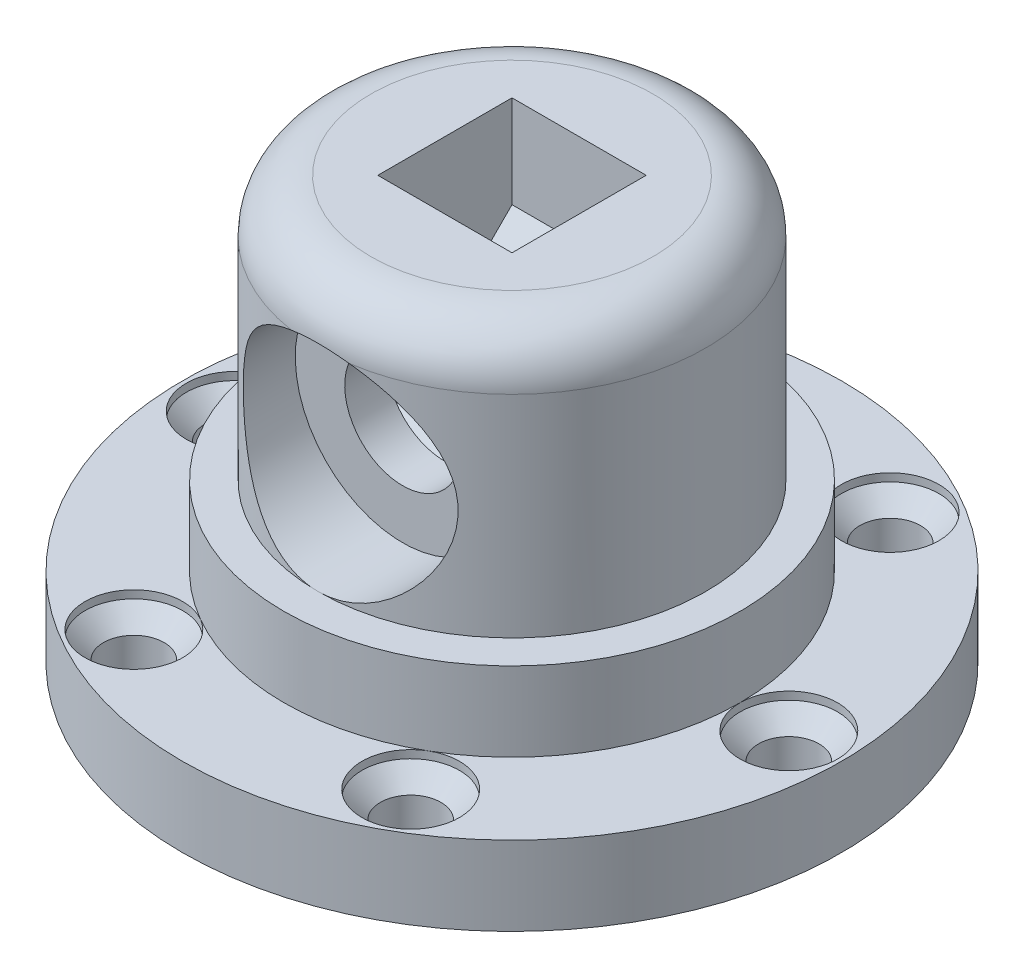
SolidWorks part; units mm, degrees
material "尼龙 101"
ref_plane "前视基准面" through (0, 0, 0) normal (0, 0, 1) x (1, 0, 0)
ref_plane "上视基准面" through (0, 0, 0) normal (0, 1, 0) x (1, 0, 0)
ref_plane "右视基准面" through (0, 0, 0) normal (1, 0, 0) x (0, 0, -1)
sketch "草图1" plane through (0, 0, 0) normal (0, 1, 0) x (1, 0, 0)
  circle A0 centre (0, 0) radius 12.5
  dimension "D1" = 25
extrude "凸台-拉伸1" add sketch "草图1" along normal blind 6
sketch "草图2" plane through (0, 6, 0) normal (0, 1, 0) x (1, 0, 0)
  line L0 (4.1, 4.1) -> (-4.1, 4.1) construction
  line L1 (2.5, 2.5) -> (-2.5, 2.5) construction
  line L2 (2.5, 2.5) -> (2.5, -2.5) construction
  line L3 (2.5, -2.5) -> (-2.5, -2.5) construction
  line L4 (-2.5, 2.5) -> (-2.5, -2.5) construction
  line L5 (2.5, 2.5) -> (-2.5, -2.5) construction
  line L6 (2.5, -2.5) -> (-2.5, 2.5) construction
  line L7 (-4.1, 4.1) -> (-4.1, -4.1) construction
  line L8 (4.1, -4.1) -> (-4.1, -4.1) construction
  line L9 (4.1, 4.1) -> (4.1, -4.1) construction
  line L11 (4.1, 4.1) -> (-4.1, 4.1) construction
  line L12 (4.1, 4.1) -> (4.1, 6.1) construction
  line L13 (4.1, 6.1) -> (-4.1, 6.1) construction
  line L14 (-4.1, 4.1) -> (-4.1, 6.1) construction
  circle A0 centre (0, 0) radius 5.7983 construction
  circle A1 centre (0, 0) radius 7.3498
  point P0 (0, 0)
  dimension "D1" = 5
  dimension "D2" = 5
  dimension "D4" = 2
  dimension "D3" = 1.6
sketch "草图3" plane through (0, 0, 0) normal (0, -1, 0) x (-1, 0, 0)
  circle A0 centre (0, 0) radius 7.5
  dimension "D1" = 15
sketch "草图4" plane through (0, 6, 0) normal (0, 1, 0) x (1, 0, 0)
  circle A0 centre (-10.5, 0) radius 1.15
  dimension "D1" = 2.3
  dimension "D2" = 10.5
extrude "切除-拉伸2" cut sketch "草图4" against normal blind 19 contours A0
extrude "切除-拉伸3" cut sketch "草图3" against normal blind 5 contours A0
chamfer "倒角2" distance 0.7 angle 45 1 edges at (-10.5, 6, 1.15)
sketch "草图8" plane through (0, 6, 0) normal (0, 1, 0) x (1, 0, 0)
  circle A0 centre (0, 0) radius 8.65
  circle A1 centre (0, 0) radius 17.4543
  dimension "D1" = 17.3
extrude "切除-拉伸4" cut sketch "草图8" against normal blind 3
pattern_circular "阵列(圆周)2" count 6 over 360 about axis through (0, 3, 0) along (0, 1, 0) of "切除-拉伸2"
extrude "凸台-拉伸2" add sketch "草图2" along normal blind 10 contours A1
sketch "草图9" plane through (0, 3, 0) normal (0, 1, 0) x (1, 0, 0)
  circle A0 centre (-10.5, 0) radius 1.85
extrude "切除-拉伸5" cut sketch "草图9" against normal blind 0.3
chamfer "倒角3" distance 0.7 angle 45 1 edges at (-10.5, 2.7, 1.15)
pattern_circular "阵列(圆周)3" count 6 over 360 about axis through (0, 6, 0) along (0, -1, 0) of "切除-拉伸5" reverse direction yes
chamfer "倒角4" distance 0.7 angle 45 5 edges at (5.25, 2.7, 10.2433) (10.5, 2.7, 1.15) (5.25, 2.7, -7.9433) (-5.25, 2.7, -7.9433) (-5.25, 2.7, 10.2433)
sketch "草图10" plane through (0, 16, 0) normal (0, 1, 0) x (1, 0, 0)
  line L1 (2.545, 2.545) -> (-2.545, 2.545)
  line L2 (2.545, 2.545) -> (2.545, -2.545)
  line L3 (2.545, -2.545) -> (-2.545, -2.545)
  line L4 (-2.545, 2.545) -> (-2.545, -2.545)
  line L5 (2.545, 2.545) -> (-2.545, -2.545) construction
  line L6 (2.545, -2.545) -> (-2.545, 2.545) construction
  point P0 (0, 0)
  dimension "D1" = 5.09
  dimension "D2" = 5.09
extrude "切除-拉伸6" cut sketch "草图10" against normal blind 8.6
sketch "草图11" plane through (0, 0, 0) normal (1, 0, 0) x (0, 0, -1)
  line L0 (-0.3049, 10.075) -> (-10.8741, 10.075)
  line L1 (-10.8741, 10.075) -> (-10.8741, 6)
  line L2 (-10.8741, 6) -> (-4.145, 6)
  line L3 (-4.145, 6) -> (-4.145, 7.875)
  line L4 (-4.145, 7.875) -> (-2.545, 7.875)
  line L5 (-2.545, 7.875) -> (-2.545, 9.125)
  line L6 (8.65, 6) -> (-8.65, 6) construction
  line L7 (-0.3049, 10.075) -> (11.1257, 10.075)
  line L8 (11.1257, 10.075) -> (11.1257, 9.125)
  line L9 (11.1257, 9.125) -> (-2.545, 9.125)
  dimension "D1" = 4.075
  dimension "D2" = 2.2
  dimension "D3" = 1.6
  dimension "D4" = 0
  dimension "D5" = 0.95
  dimension "D6" = 0
revolve "切除-旋转1" cut sketch "草图11" angle 360 about L0
fillet "圆角1" radius 2 1 edges at (0, 16, 7.3498)
chamfer "倒角5" distance 5.09 angle 45 1 edges at (0, 7.4, -2.545)
